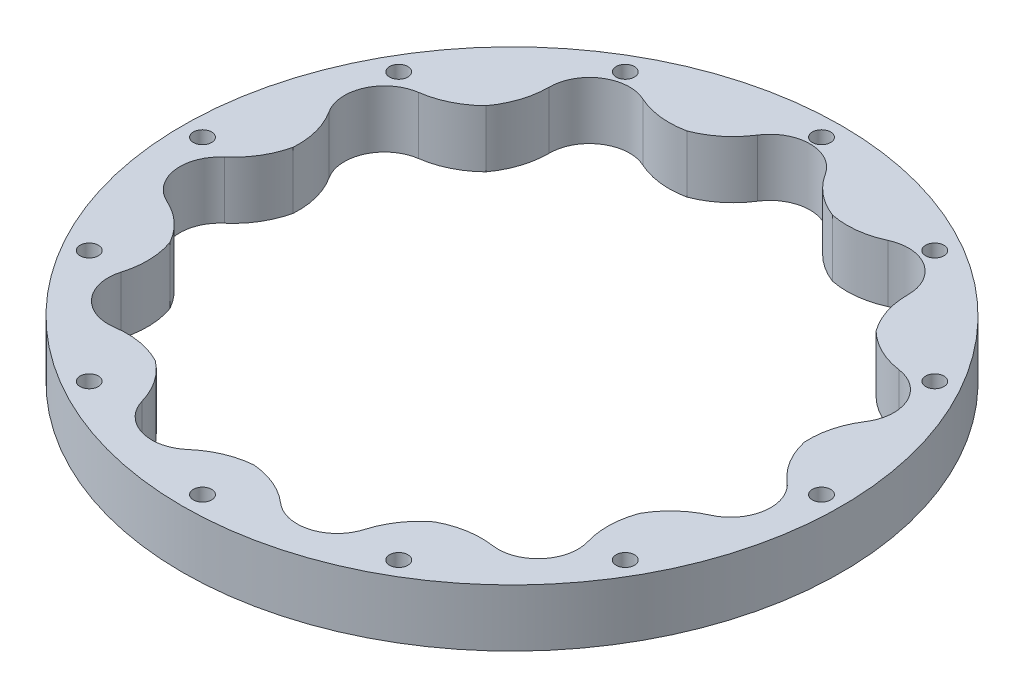
SolidWorks part; units mm, degrees
ref_plane "Front Plane" through (0, 0, 0) normal (0, 0, 1) x (1, 0, 0)
ref_plane "Top Plane" through (0, 0, 0) normal (0, 1, 0) x (1, 0, 0)
ref_plane "Right Plane" through (0, 0, 0) normal (1, 0, 0) x (0, 0, -1)
sketch "Sketch1" plane through (0, 0, 0) normal (0, 1, 0) x (1, 0, 0)
  circle A0 centre (0, 0) radius 45
  circle A1 centre (0, 45) radius 7
  circle A2 centre (24.3288, 37.8564) radius 7
  circle A3 centre (40.9334, 18.6937) radius 7
  circle A4 centre (44.542, -6.4042) radius 7
  circle A5 centre (34.0087, -29.4687) radius 7
  circle A6 centre (12.678, -43.1772) radius 7
  circle A7 centre (-12.678, -43.1772) radius 7
  circle A8 centre (-34.0087, -29.4687) radius 7
  circle A9 centre (-44.542, -6.4042) radius 7
  circle A10 centre (-40.9334, 18.6937) radius 7
  circle A11 centre (-24.3288, 37.8564) radius 7
  circle A12 centre (0, 0) radius 57.5
  circle A13 centre (0, 0) radius 54 construction
  circle A14 centre (0, 54) radius 1.6
  circle A15 centre (27, 46.7654) radius 1.6
  circle A16 centre (46.7654, 27) radius 1.6
  circle A17 centre (54, 0) radius 1.6
  circle A18 centre (46.7654, -27) radius 1.6
  circle A19 centre (27, -46.7654) radius 1.6
  circle A20 centre (0, -54) radius 1.6
  circle A21 centre (-27, -46.7654) radius 1.6
  circle A22 centre (-46.7654, -27) radius 1.6
  circle A23 centre (-54, 0) radius 1.6
  circle A24 centre (-46.7654, 27) radius 1.6
  circle A25 centre (-27, 46.7654) radius 1.6
  point P27 (0, 0)
  point P54 (0, 0)
  dimension "D1" = 90
  dimension "D2" = 14
  dimension "D4" = 115
  dimension "D5" = 108
  dimension "D6" = 3.2
  dimension "D3" = 11
  dimension "D7" = 12
extrude "Boss-Extrude1" add sketch "Sketch1" along normal blind 10 contours A12 A25 A24 A23 A22 A21 A20 A19 A18 A17 A16 A15 A14 A11 A0 A1 A2 A3 A4 A5 A6 A7 A8 A9 A10 region at (-55.8737, 0, 0)
fillet "Fillet1" radius 14 22 edges at (44.9962, 5, -0.5811) (43.3373, 5, -12.1194) (38.1674, 5, 23.838) (43.0099, 5, 13.2344) (29.0271, 5, 34.3864) (19.2207, 5, 40.6886) (5.8285, 5, 44.6209) (-5.8285, 5, 44.6209) (-19.2207, 5, 40.6886) (-29.0271, 5, 34.3864) (-43.0099, 5, 13.2344) (-38.1674, 5, 23.838) (-44.9962, 5, -0.5811) (-43.3373, 5, -12.1194) (-37.5391, 5, -24.8156) (-29.9054, 5, -33.6254) (37.5391, 5, -24.8156) (29.9054, 5, -33.6254) (18.1636, 5, -41.1714) (6.9788, 5, -44.4556) (-6.9788, 5, -44.4556) (-18.1636, 5, -41.1714)
